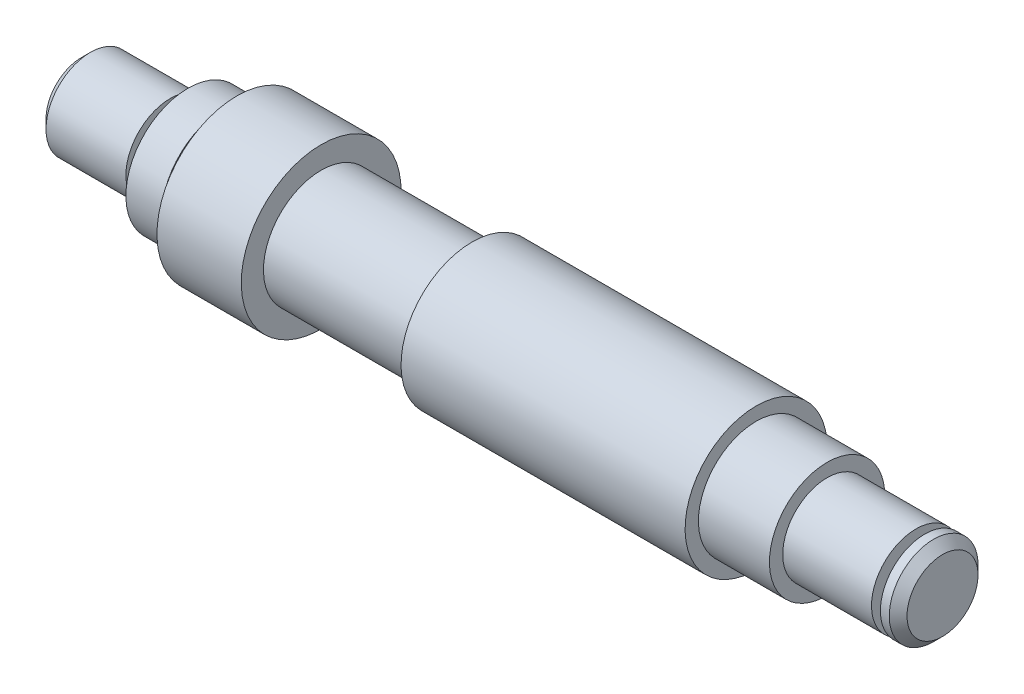
SolidWorks part; units mm, degrees
ref_plane "Plan de face" through (0, 0, 0) normal (0, 0, 1) x (1, 0, 0)
ref_plane "Plan de dessus" through (0, 0, 0) normal (0, 1, 0) x (1, 0, 0)
ref_plane "Plan de droite" through (0, 0, 0) normal (1, 0, 0) x (0, 0, -1)
sketch "Sketch1" plane through (0, 0, 0) normal (0, 0, 1) x (1, 0, 0)
  line L0 (0, 0) -> (0, 2.5)
  line L1 (0, 2.5) -> (-1, 2.5)
  line L2 (-1, 2.5) -> (-1, 1.5)
  line L3 (-1, 1.5) -> (-1.5, 1.5)
  line L4 (-1.5, 1.5) -> (-1.5, 2.5)
  line L5 (-1.5, 2.5) -> (-6.5, 2.5)
  line L6 (-6.5, 2.5) -> (-6.5, 3.25)
  line L7 (-6.5, 3.25) -> (-10.5, 3.25)
  line L8 (-10.5, 3.25) -> (-10.5, 4)
  line L9 (-10.5, 4) -> (-26.5, 4)
  line L10 (-26.5, 4) -> (-26.5, 3.25)
  line L11 (-26.5, 3.25) -> (-35, 3.25)
  line L12 (-35, 3.25) -> (-35, 4.5)
  line L13 (-35, 4.5) -> (-39.75, 4.5)
  line L14 (-39.75, 4.5) -> (-39.75, 3)
  line L15 (-39.75, 3) -> (-40.5, 3)
  line L16 (-40.5, 3) -> (-40.5, 3.5)
  line L17 (-40.5, 3.5) -> (-42.5, 3.5)
  line L18 (-42.5, 3.5) -> (-42.5, 2)
  line L19 (-42.5, 2) -> (-43.5, 2)
  line L20 (-43.5, 2) -> (-43.5, 2.5)
  line L21 (-43.5, 2.5) -> (-48.5, 2.5)
  line L22 (-48.5, 2.5) -> (-48.5, 0)
  line L23 (0, 0) -> (-48.5, 0)
  dimension "D1" = 2.5
  dimension "D2" = 1
  dimension "D20" = 1
  dimension "D3" = 1
  dimension "D4" = 0.5
  dimension "D5" = 5
  dimension "D6" = 0.75
  dimension "D7" = 4
  dimension "D8" = 0.75
  dimension "D9" = 1
  dimension "D10" = 16
  dimension "D11" = 0.75
  dimension "D12" = 8.5
  dimension "D13" = 1.25
  dimension "D14" = 4.75
  dimension "D15" = 1.5
  dimension "D16" = 0.75
  dimension "D17" = 0.5
  dimension "D18" = 2
  dimension "D19" = 1.5
  dimension "D21" = 0.5
  dimension "D22" = 5
revolve "Revolve1" add sketch "Sketch1" angle 360 about L23
cosmetic thread "Cosmetic Thread1" parameters "D1"=5, "D2"=4
chamfer "Chamfer1" distance 0.5 angle 45 2 edges at (0, 2.5, 0) (-48.5, 2.5, 0)
